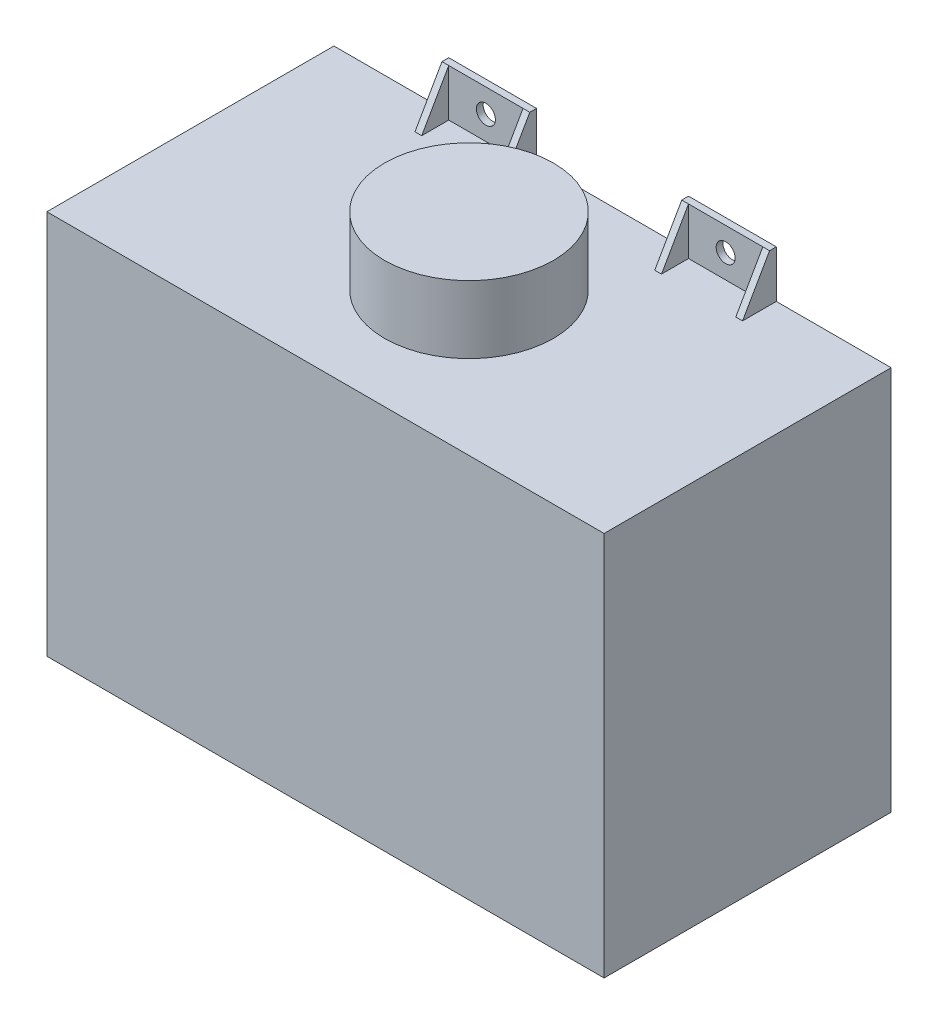
SolidWorks part; units mm, degrees
material "PE Low/Medium Density"
ref_plane "X-Y Datum" through (0, 0, 0) normal (0, 0, 1) x (1, 0, 0)
ref_plane "X-Z Datum" through (0, 0, 0) normal (0, 1, 0) x (1, 0, 0)
ref_plane "Y-Z Datum" through (0, 0, 0) normal (1, 0, 0) x (0, 0, -1)
sketch "Sketch1" plane through (0, 0, 0) normal (0, 1, 0) x (1, 0, 0)
  line L1 (104.775, 53.975) -> (-104.775, 53.975)
  line L2 (104.775, 53.975) -> (104.775, -53.975)
  line L3 (104.775, -53.975) -> (-104.775, -53.975)
  line L4 (-104.775, 53.975) -> (-104.775, -53.975)
  line L5 (104.775, 53.975) -> (-104.775, -53.975) construction
  line L6 (104.775, -53.975) -> (-104.775, 53.975) construction
  point P0 (0, 0)
  dimension "D1" = 209.55
  dimension "D2" = 107.95
extrude "Boss-Extrude1" add sketch "Sketch1" along normal blind 144.78
sketch "Sketch2" plane through (0, 144.78, 0) normal (0, 1, 0) x (1, 0, 0)
  circle A0 centre (0, 0) radius 31.75
  dimension "D1" = 63.5
extrude "Boss-Extrude2" add sketch "Sketch2" along normal blind 25.4
sketch "Sketch3" plane through (0, 144.78, 0) normal (0, 1, 0) x (1, 0, 0)
  line L0 (-61.595, 53.975) -> (-61.595, 41.275)
  line L1 (104.775, 53.975) -> (-104.775, 53.975) construction
  line L2 (-61.595, 41.275) -> (-59.055, 41.275)
  line L3 (-59.055, 41.275) -> (-59.055, 51.435)
  line L4 (-59.055, 51.435) -> (-31.115, 51.435)
  line L5 (-31.115, 51.435) -> (-31.115, 41.275)
  line L6 (-31.115, 41.275) -> (-28.575, 41.275)
  line L7 (-28.575, 41.275) -> (-28.575, 53.975)
  line L8 (-28.575, 53.975) -> (-61.595, 53.975)
  line L9 (-104.775, 53.975) -> (-104.775, -53.975) construction
  line L10 (0, 53.975) -> (0, -53.975) construction
  line L11 (-104.775, -53.975) -> (104.775, -53.975) construction
  line L12 (28.575, 53.975) -> (61.595, 53.975)
  line L13 (28.575, 41.275) -> (28.575, 53.975)
  line L14 (31.115, 41.275) -> (28.575, 41.275)
  line L15 (31.115, 51.435) -> (31.115, 41.275)
  line L16 (59.055, 51.435) -> (31.115, 51.435)
  line L17 (59.055, 41.275) -> (59.055, 51.435)
  line L18 (61.595, 41.275) -> (59.055, 41.275)
  line L19 (61.595, 53.975) -> (61.595, 41.275)
  dimension "D1" = 12.7
  dimension "D2" = 2.54
  dimension "D3" = 2.54
  dimension "D4" = 43.18
  dimension "D5" = 76.2
extrude "Boss-Extrude3" add sketch "Sketch3" along normal blind 17.78
sketch "Sketch5" plane through (31.115, 0, 0) normal (1, 0, 0) x (0, 0, -1)
  line L0 (41.275, 144.78) -> (51.435, 162.56)
  line L4 (41.275, 144.78) -> (51.435, 144.78)
  line L5 (51.435, 144.78) -> (51.435, 162.56)
  line L6 (51.435, 162.56) -> (41.275, 162.56)
  line L7 (41.275, 162.56) -> (41.275, 144.78)
  line L8 (41.275, 144.78) -> (51.435, 144.78)
  line L9 (51.435, 144.78) -> (51.435, 162.56)
  line L10 (51.435, 162.56) -> (41.275, 162.56)
  line L11 (41.275, 162.56) -> (41.275, 144.78)
  line M7 (51.435, 162.56) -> (41.275, 162.56)
  line M8 (41.275, 162.56) -> (41.275, 144.78)
  dimension "D1" = 0
extrude "Cut-Extrude2" cut sketch "Sketch5" against normal through all both and the other way through all contours L0 M8 M7 region at (31.115, 156.6333, -44.6617)
hole_wizard "1/4 Clearance Hole1" positions "3DSketch1" profile "Sketch6" hole size "1/4" standard "ANSI Inch" end condition through all
sketch3d "3DSketch1"
  line L0 (-59.055, 162.56, -51.435) -> (-31.115, 144.78, -51.435)
  line L1 (31.115, 162.56, -51.435) -> (59.055, 144.78, -51.435)
  point P0 (-45.085, 153.67, -51.435)
  point P10 (45.085, 153.67, -51.435)
sketch "Sketch6" plane through (-45.085, 153.67, -51.435) normal (1, 0, 0) x (0, -1, 0)
  line L0 (0, 0) -> (0, 2.54)
  line L1 (0, 2.54) -> (3.5712, 2.54)
  line L2 (3.5712, 2.54) -> (3.5712, 0)
  line L5 (3.5712, 0) -> (0, 0)
  line L11 (0, -6.35) -> (0, 107.95) construction
  dimension "Thru Hole Dia." = 7.1425
  dimension "Thru Hole Depth" = 2.54
